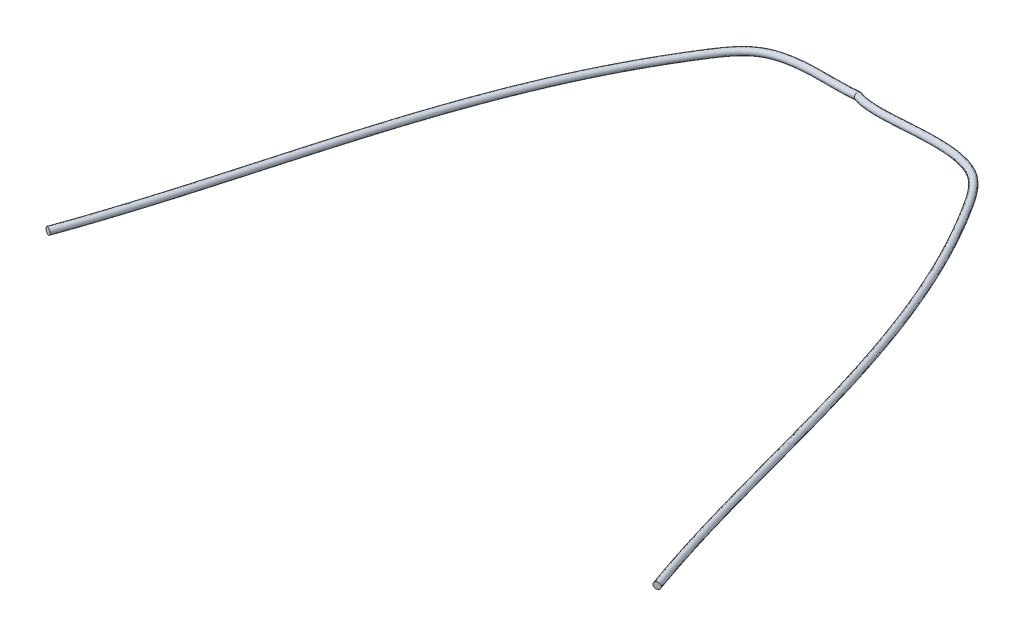
SolidWorks part; units mm, degrees
ref_plane "Front Plane" through (0, 0, 0) normal (0, 0, 1) x (1, 0, 0)
ref_plane "Top Plane" through (0, 0, 0) normal (0, 1, 0) x (1, 0, 0)
ref_plane "Right Plane" through (0, 0, 0) normal (1, 0, 0) x (0, 0, -1)
ref_plane "Plane1" through (0, 20.5189, 0) normal (0, 1, 0) x (1, 0, 0)
sketch "Sketch56" plane through (0, 20.5189, 0) normal (0, 1, 0) x (1, 0, 0)
  arc A0 (8.5154, 54.6974) -> (-0.6338, 48.7338) centre (8.5154, 44.6974) ccw construction
  arc A1 (-14.8575, 16.4933) -> (-15.7084, 12.4569) centre (-5.7084, 12.4569) ccw construction
  spline S0 degree 3 poles (16.4338, 54.9311) (12.6283, 54.4219) (4.1946, 55.9877) (-14.7225, 27.9739) (-18.2026, 0.7646) (-27.0872, -23.8888) knots 0 0 0 0 0.140616 0.199514 1 1 1 1
sketch "Sketch19" plane through (0, 20.5189, 0) normal (0, 1, 0) x (1, 0, 0)
  arc A0 (39.212, 48.7338) -> (30.0628, 54.6974) centre (30.0628, 44.6974) ccw construction
  arc A1 (53.7305, 13.7174) -> (52.8796, 17.7538) centre (43.7305, 13.7174) ccw construction
  spline S0 degree 3 poles (16.4338, 54.9311) (20.7474, 53.2003) (33.2369, 57.6067) (53.4235, 27.9951) (56.4467, 0.4076) (65.307, -24.2889) knots 0 0 0 0 0.188165 0.243624 1 1 1 1
sweep "Sweep2" add path "Sketch19" circular profile diameter 1 parameters "D3"=1
sweep "Sweep3" add path "Sketch56" circular profile diameter 1 parameters "D3"=1
